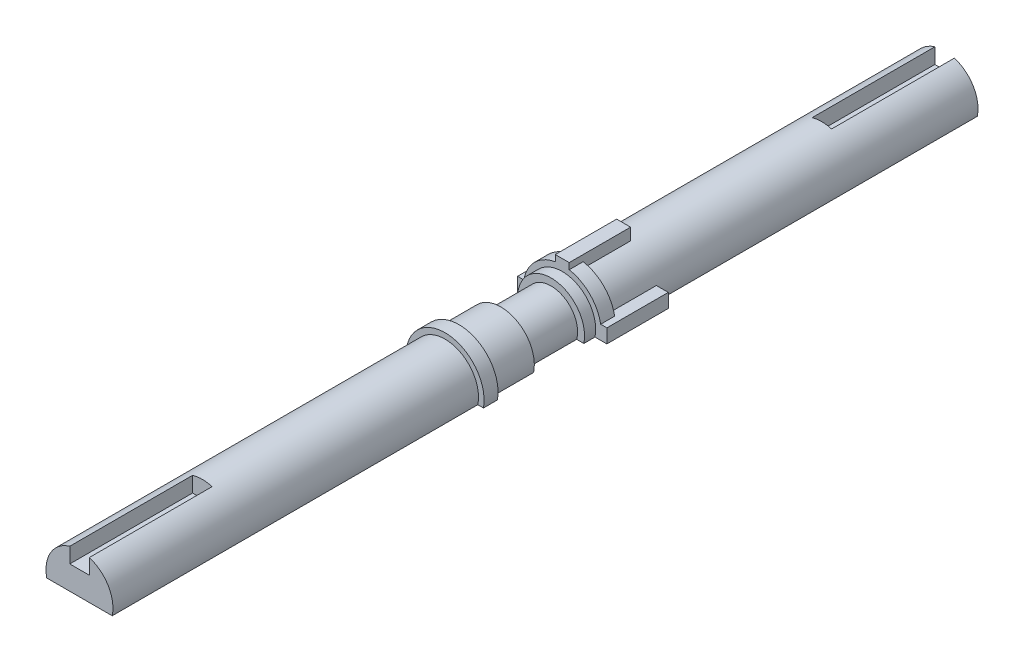
SolidWorks part; units mm, degrees
ref_plane "Front Plane" through (0, 0, 0) normal (0, 0, 1) x (1, 0, 0)
ref_plane "Top Plane" through (0, 0, 0) normal (0, 1, 0) x (1, 0, 0)
ref_plane "Right Plane" through (0, 0, 0) normal (1, 0, 0) x (0, 0, -1)
sketch "Sketch1" plane through (0, 0, 0) normal (0, 0, 1) x (1, 0, 0)
  line L0 (-11.1312, -1.25) -> (14.2968, -1.25) construction
  line L1 (-11.6369, 1.25) -> (-5.8683, 1.25) construction
  line L3 (8, 1.25) -> (5.8683, 1.25)
  line L4 (8, 1.25) -> (8, -1.25)
  line L5 (8, -1.25) -> (-8, -1.25)
  line L6 (-8, 1.25) -> (-8, -1.25)
  line L9 (-1.25, 8) -> (1.25, 8)
  line L10 (-1.25, 8) -> (-1.25, 5.8683)
  line L12 (1.25, 8) -> (1.25, 5.8683)
  line L18 (-5.8683, 1.25) -> (-8, 1.25)
  line L24 (5.8683, 1.25) -> (15.6333, 1.25) construction
  arc A2 (5.8683, 1.25) -> (1.25, 5.8683) centre (0, 0) ccw
  arc A3 (-1.25, 5.8683) -> (-5.8683, 1.25) centre (0, 0) ccw
  dimension "D2" = 1.25
  dimension "D3" = 2.5
  dimension "D4" = 16
  dimension "D6" = 2.5
extrude "Boss-Extrude1" add sketch "Sketch1" along normal blind 8
sketch "Sketch3" plane through (0, 0, 8) normal (0, 0, 1) x (1, 0, 0)
  line L0 (-5.8683, -1.25) -> (5.8683, -1.25)
  arc A0 (5.8683, -1.25) -> (-5.8683, -1.25) centre (0, 0) ccw
extrude "Boss-Extrude2" add sketch "Sketch3" along normal blind 26
sketch "Sketch5" plane through (0, 0, 8) normal (0, 0, 1) x (1, 0, 0)
  line L0 (-6.8875, -1.25) -> (6.8875, -1.25)
  arc A0 (6.8875, -1.25) -> (-6.8875, -1.25) centre (0, 0) ccw
extrude "Boss-Extrude3" add sketch "Sketch5" against normal blind 2.5
sketch "Sketch8" plane through (0, 0, 0) normal (0, 0, -1) x (-1, 0, 0)
  line L0 (-5.8683, -1.25) -> (5.8683, -1.25)
  arc A0 (5.8683, -1.25) -> (-5.8683, -1.25) centre (0, 0) ccw
sketch "Sketch9" plane through (0, 0, 34) normal (0, 0, 1) x (1, 0, 0)
  line L0 (-6.8875, -1.25) -> (6.8875, -1.25)
  arc A0 (6.8875, -1.25) -> (-6.8875, -1.25) centre (0, 0) ccw
extrude "Boss-Extrude4" add sketch "Sketch9" against normal blind 2.5 from offset 5 separate body offset against normal yes
sketch "Sketch10" plane through (0, 0, 0) normal (0, 0, -1) x (-1, 0, 0)
  line L0 (-5.8683, -1.25) -> (5.8683, -1.25)
  arc A0 (5.8683, -1.25) -> (-5.8683, -1.25) centre (0, 0) ccw
extrude "Boss-Extrude5" add sketch "Sketch10" along normal blind 8
sketch "Sketch12" plane through (0, 0, 0) normal (0, 0, -1) x (-1, 0, 0)
  line L1 (-1.25, 8) -> (1.25, 8)
  line L2 (-1.25, 8) -> (-1.25, 5.8683)
  line L3 (-1.25, 5.8683) -> (1.25, 5.8683)
  line L4 (1.25, 8) -> (1.25, 5.8683)
  line L5 (-1.25, 8) -> (1.25, 5.8683) construction
  line L6 (-1.25, 5.8683) -> (1.25, 8) construction
  line L7 (8, 1.25) -> (5.8683, 1.25)
  line L8 (8, 1.25) -> (8, -1.25)
  line L9 (8, -1.25) -> (5.8683, -1.25)
  line L10 (5.8683, 1.25) -> (5.8683, -1.25)
  line L11 (8, 1.25) -> (5.8683, -1.25) construction
  line L12 (8, -1.25) -> (5.8683, 1.25) construction
  line L13 (-8, 1.25) -> (-5.8683, 1.25)
  line L14 (-8, 1.25) -> (-8, -1.25)
  line L15 (-8, -1.25) -> (-5.8683, -1.25)
  line L16 (-5.8683, 1.25) -> (-5.8683, -1.25)
  line L17 (-8, 1.25) -> (-5.8683, -1.25) construction
  line L18 (-8, -1.25) -> (-5.8683, 1.25) construction
  point P4 (0, 6.9342)
  point P11 (6.9342, 0)
  point P18 (-6.9342, 0)
extrude "Boss-Extrude6" add sketch "Sketch12" along normal blind 3
ref_plane "Plane1" through (0, 0, 0) normal (1, 0, 0) x (0, 0, -1)
sketch "Sketch13" plane through (0, 0, 0) normal (1, 0, 0) x (0, 0, -1)
  line L0 (-34, 6) -> (-34, -1.25) construction
  line L1 (60.5, -6) -> (-94.5, -6) construction
  line L2 (60.5, -6) -> (60.5, 6) construction
  line L3 (60.5, 6) -> (-94.5, 6) construction
  line L4 (-94.5, -6) -> (-94.5, 6) construction
  line L5 (60.5, -6) -> (-94.5, 6) construction
  line L6 (60.5, 6) -> (-94.5, -6) construction
  line L7 (21, 16.6876) -> (21, -23.7224) construction
  line L8 (63, 13.4624) -> (63, -19.5486) construction
  line L9 (-55, 23.9917) -> (-55, -22.9635) construction
  line L10 (-97, 20.1974) -> (-97, -24.8607) construction
  line L11 (8, -1.25) -> (8, 6) construction
  line L13 (-17, 18.6576) -> (-17, -28.9893) construction
  line L14 (-67.2962, 0) -> (33.9861, 0) construction
  point P0 (-17, 0)
  dimension "D1" = 155
  dimension "D2" = 13
  dimension "D3" = 55
  dimension "D4" = 160
  dimension "D5" = 38
  dimension "D6" = 52.5
  dimension "D7" = 60.5
sketch "Sketch14" plane through (0, 0, 34) normal (0, 0, 1) x (1, 0, 0)
  line L1 (-5.8683, -1.25) -> (5.8683, -1.25)
  line L2 (-5.8683, -1.25) -> (5.8683, -1.25)
  arc A1 (5.8683, -1.25) -> (-5.8683, -1.25) centre (0, 0) ccw
  arc A2 (5.8683, -1.25) -> (-5.8683, -1.25) centre (0, 0) ccw
  dimension "D1" = 0
extrude "Boss-Extrude7" add sketch "Sketch14" along normal blind 60.5
sketch "Sketch15" plane through (0, 0, -8) normal (0, 0, -1) x (-1, 0, 0)
  line L1 (-5.8683, -1.25) -> (5.8683, -1.25)
  line L2 (-5.8683, -1.25) -> (5.8683, -1.25)
  arc A1 (5.8683, -1.25) -> (-5.8683, -1.25) centre (0, 0) ccw
  arc A2 (5.8683, -1.25) -> (-5.8683, -1.25) centre (0, 0) ccw
  dimension "D1" = 0
extrude "Boss-Extrude8" add sketch "Sketch15" along normal blind 52.5
sketch "Sketch16" plane through (0, 0, -60.5) normal (0, 0, -1) x (-1, 0, 0)
  line L9 (-5.8683, -1.25) -> (5.8683, -1.25)
  line L18 (-1.7621, 5.7354) -> (-1.7621, 2.9941)
  line L20 (1.7379, 5.7428) -> (1.7379, 2.9941)
  line L21 (-1.7621, 2.9941) -> (1.7379, 2.9941)
  arc A1 (5.8683, -1.25) -> (-5.8683, -1.25) centre (0, 0) ccw
  arc A2 (1.7379, 5.7428) -> (-1.7621, 5.7354) centre (0, 0) ccw
  point P0 (-0.0059, 0.0121)
  point P5 (-0.0059, 0.0121)
  point P24 (0, 0)
  dimension "D3" = 0
extrude "Cut-Extrude1" cut sketch "Sketch16" against normal blind 22
ref_plane "Plane2" through (0, 0, 17) normal (0, 0, 1) x (1, 0, 0)
mirror "Mirror1" about plane through (0, 0, 17) normal (0, 0, 1) of "Cut-Extrude1"
sketch "Sketch17" plane through (0, 0, 8) normal (0, 0, 1) x (1, 0, 0)
  line L0 (-9.5284, -1.25) -> (-4.5826, -1.25)
  line L1 (4.5826, -1.25) -> (9.5284, -1.25)
  arc A0 (4.5826, -1.25) -> (-4.5826, -1.25) centre (0, 0) ccw
  arc A1 (9.5284, -1.25) -> (-9.5284, -1.25) centre (0, 0) ccw
  dimension "D1" = 9.5
extrude "Cut-Extrude2" cut sketch "Sketch17" along normal blind 9 from offset 2
